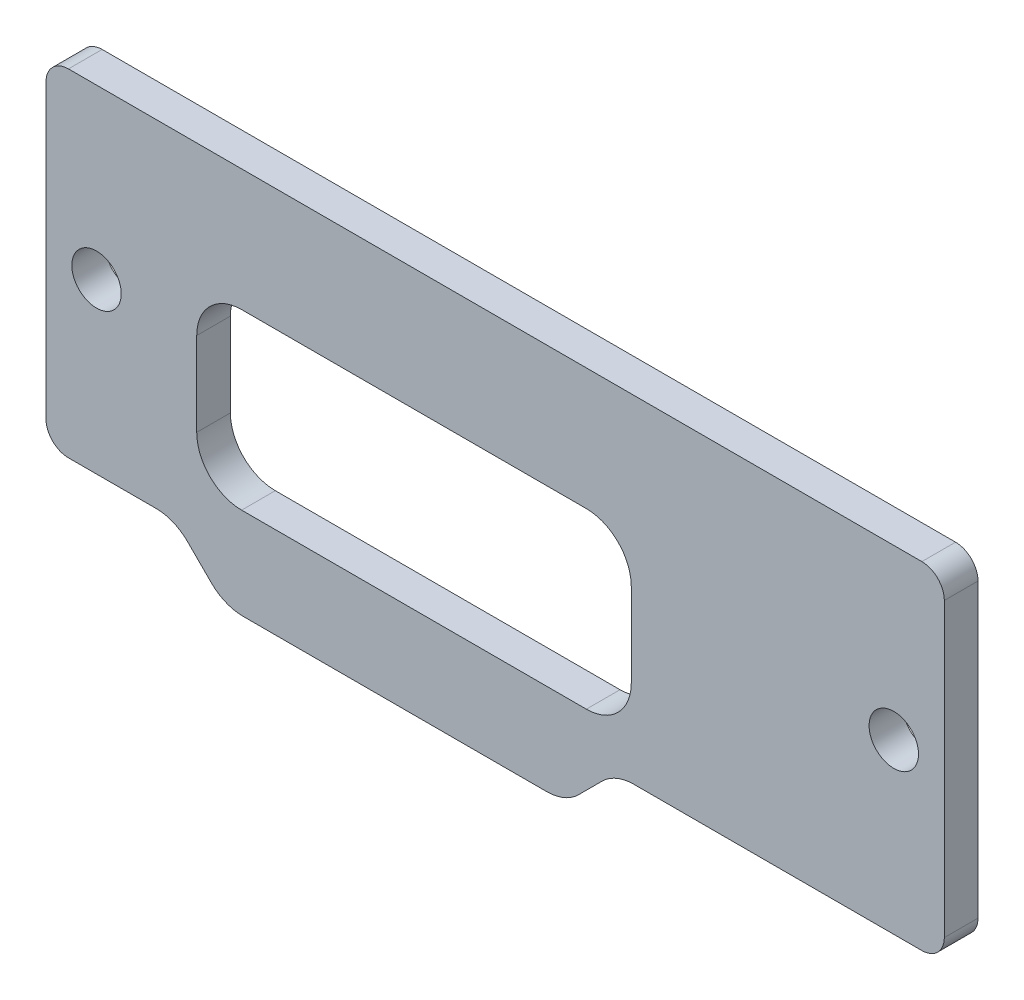
SolidWorks part; units mm, degrees
material "PA 类型 6"
ref_plane "前视基准面" through (0, 0, 0) normal (0, 0, 1) x (1, 0, 0)
ref_plane "上视基准面" through (0, 0, 0) normal (0, 1, 0) x (1, 0, 0)
ref_plane "右视基准面" through (0, 0, 0) normal (1, 0, 0) x (0, 0, -1)
sketch "草图1" plane through (0, 0, 0) normal (0, 0, 1) x (1, 0, 0)
  line L1 (-21.7384, 9.3368) -> (13.7616, 9.3368) construction
  line L2 (-21.7384, 9.3368) -> (-21.7384, -0.6632) construction
  line L3 (-21.7384, -0.6632) -> (13.7616, -0.6632) construction
  line L4 (13.7616, 9.3368) -> (13.7616, -0.6632) construction
  line L5 (-21.7384, 9.3368) -> (13.7616, -0.6632) construction
  line L6 (-21.7384, -0.6632) -> (13.7616, 9.3368) construction
  line L7 (-23.9884, 11.8368) -> (16.0116, 11.8368)
  line L8 (-23.9884, 11.8368) -> (-23.9884, -3.1632)
  line L9 (-23.9884, -3.1632) -> (16.0116, -3.1632)
  line L10 (16.0116, 11.8368) -> (16.0116, -3.1632)
  line L11 (-23.9884, 11.8368) -> (16.0116, -3.1632) construction
  line L12 (-23.9884, -3.1632) -> (16.0116, 11.8368) construction
  circle A0 centre (-21.7384, 9.3368) radius 1.1 construction
  circle A1 centre (-21.7384, -0.6632) radius 1.1 construction
  circle A2 centre (13.7616, -0.6632) radius 1.1 construction
  circle A3 centre (13.7616, 9.3368) radius 1.1 construction
  circle A4 centre (-21.7384, 4.3368) radius 1.1
  circle A5 centre (13.7616, 4.3368) radius 1.1
  point P0 (-3.9884, 4.3368)
  point P9 (-3.9884, 4.3368)
  dimension "D3" = 40
  dimension "D4" = 15
  dimension "D1" = 10
  dimension "D2" = 35.5
extrude "凸台-拉伸1" add sketch "草图1" along normal blind 1.5
sketch "草图2" plane through (0, 0, 1.5) normal (0, 0, 1) x (1, 0, 0)
  line L7 (-17.2774, 6.4097) -> (2.072, 6.4097)
  line L8 (-17.2774, 6.4097) -> (-17.2774, -1.3235)
  line L9 (-17.2774, -1.3235) -> (2.072, -1.3235)
  line L10 (2.072, 6.4097) -> (2.072, -1.3235)
  line L11 (-17.2774, 6.4097) -> (2.072, -1.3235) construction
  line L12 (-17.2774, -1.3235) -> (2.072, 6.4097) construction
  point P8 (-7.6027, 2.5431)
extrude "切除-拉伸1" cut sketch "草图2" against normal blind 1.5
fillet "圆角2" radius 1 4 edges at (16.0116, 11.8368, 0.75) (16.0116, -3.1632, 0.75) (-23.9884, -3.1632, 0.75) (-23.9884, 11.8368, 0.75)
fillet "圆角3" radius 2 4 edges at (2.072, 6.4097, 0.75) (2.072, -1.3235, 0.75) (-17.2774, -1.3235, 0.75) (-17.2774, 6.4097, 0.75)
sketch "草图3" plane through (0, 0, 1.5) normal (0, 0, 1) x (1, 0, 0)
  line L0 (-18.8396, -2.5877) -> (-16.0408, -5.3865)
  line L1 (-16.0408, -5.3865) -> (-0.8641, -5.3865)
  line L2 (-0.8641, -5.3865) -> (2.8881, -1.6343)
  line L3 (2.8881, -1.6343) -> (-18.8396, -2.5877)
  line L4 (-22.9884, -3.1632) -> (15.0116, -3.1632) construction
  dimension "D1" = 45
  dimension "D2" = 45
extrude "凸台-拉伸2" add sketch "草图3" against normal up to surface (1.5 mm away) up to face at (-7.6027, 2.5431, 0)
fillet "圆角4" radius 2 4 edges at (1.3592, -3.1632, 0.75) (-0.8641, -5.3865, 0.75) (-18.2641, -3.1632, 0.75) (-16.0408, -5.3865, 0.75)
